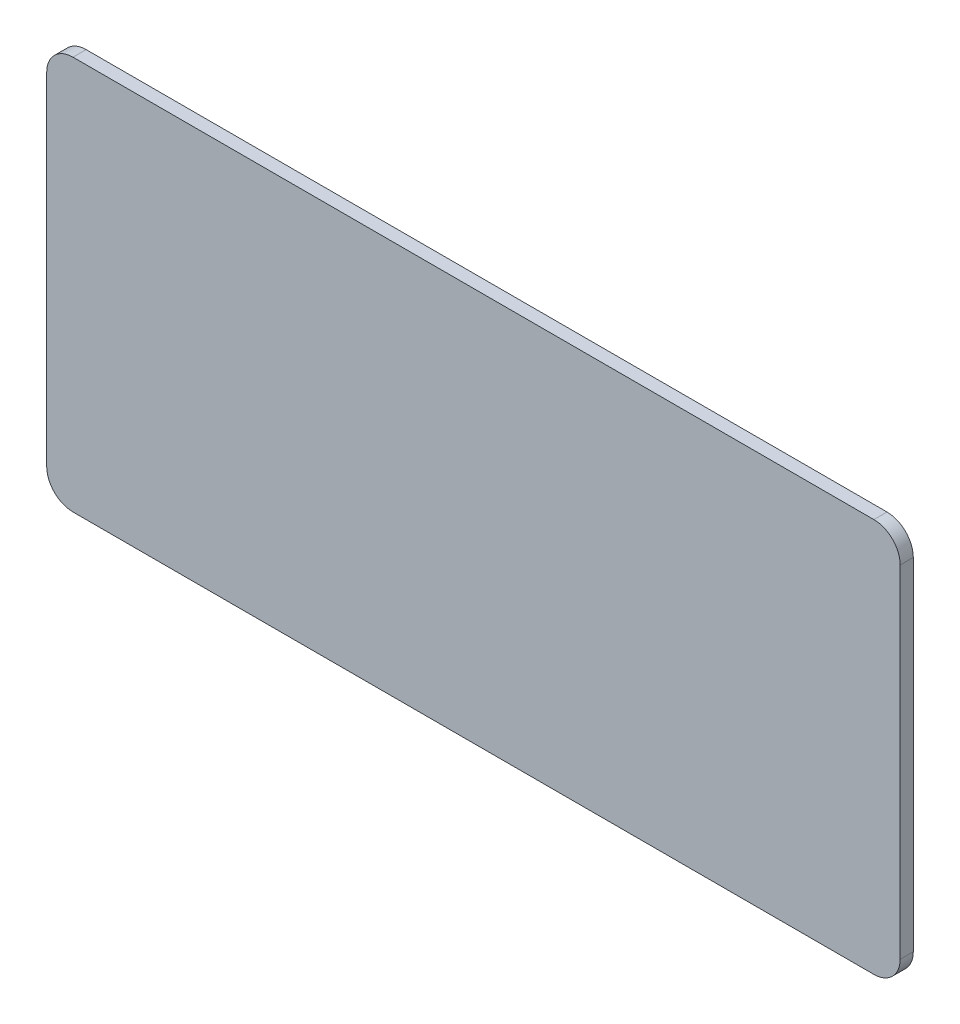
SolidWorks part; units mm, degrees
ref_plane "Front Plane" through (0, 0, 0) normal (0, 0, 1) x (1, 0, 0)
ref_plane "Top Plane" through (0, 0, 0) normal (0, 1, 0) x (1, 0, 0)
ref_plane "Right Plane" through (0, 0, 0) normal (1, 0, 0) x (0, 0, -1)
sketch "Sketch1" plane through (0, 0, 0) normal (0, 0, 1) x (1, 0, 0)
  line L0 (125.9407, 9.445) -> (125.9407, -9.555) construction
  line L1 (100.9407, 9.445) -> (150.9407, 9.445) construction
  line L2 (150.9407, -9.555) -> (100.9407, -9.555) construction
  line L3 (93.4407, 14.945) -> (93.4407, -15.055) construction
  line L4 (93.4407, -15.055) -> (158.4407, -15.055) construction
  line L5 (158.4407, -15.055) -> (158.4407, 14.945) construction
  line L6 (158.4407, 14.945) -> (93.4407, 14.945) construction
  line L7 (95.4407, 14.945) -> (95.4407, -15.055) construction
  line L8 (158.4407, -15.055) -> (93.4407, 14.945) construction
  line L9 (158.4407, 14.945) -> (93.4407, -15.055) construction
  line L10 (93.4407, -13.055) -> (158.4407, -13.055) construction
  line L11 (156.4407, -15.055) -> (156.4407, 14.945) construction
  line L12 (158.4407, 12.945) -> (93.4407, 12.945) construction
  line L13 (93.4407, -13.055) -> (93.4407, 12.945)
  line L14 (95.4407, 14.945) -> (156.4407, 14.945)
  line L15 (158.4407, 12.945) -> (158.4407, -13.055)
  line L16 (156.4407, -15.055) -> (95.4407, -15.055)
  arc A0 (93.4407, 12.945) -> (95.4407, 14.945) centre (95.4407, 12.945) cw
  arc A1 (156.4407, 14.945) -> (158.4407, 12.945) centre (156.4407, 12.945) cw
  arc A2 (158.4407, -13.055) -> (156.4407, -15.055) centre (156.4407, -13.055) cw
  arc A3 (95.4407, -15.055) -> (93.4407, -13.055) centre (95.4407, -13.055) cw
  point P6 (125.9407, -0.055)
  dimension "D1" = 65
  dimension "D2" = 30
  dimension "D3" = 2
extrude "Boss-Extrude1" add sketch "Sketch1" against normal blind 1
sketch "Sketch2" plane through (0, 0, -1) normal (0, 0, -1) x (-1, 0, 0)
  line L0 (-150.9407, 6.945) -> (-100.9407, 6.945) construction
  line L1 (-150.9407, -9.555) -> (-150.9407, 9.445) construction
  line L2 (-100.9407, -9.555) -> (-100.9407, 9.445) construction
  line L3 (-150.9407, -7.055) -> (-100.9407, -7.055) construction
  line L4 (-103.4407, 9.445) -> (-103.4407, -9.555) construction
  line L5 (-100.9407, 9.445) -> (-150.9407, 9.445) construction
  line L6 (-150.9407, -9.555) -> (-100.9407, -9.555) construction
  line L7 (-148.4407, 9.445) -> (-148.4407, -9.555) construction
  line L8 (-148.4407, 9.445) -> (-103.4407, 9.445)
  line L9 (-100.9407, 6.945) -> (-100.9407, -7.055)
  line L10 (-103.4407, -9.555) -> (-148.4407, -9.555)
  line L12 (-150.9407, -7.055) -> (-150.9407, 6.945)
  arc A0 (-150.9407, 6.945) -> (-148.4407, 9.445) centre (-148.4407, 6.945) cw
  arc A1 (-103.4407, 9.445) -> (-100.9407, 6.945) centre (-103.4407, 6.945) cw
  arc A2 (-103.4407, -9.555) -> (-100.9407, -7.055) centre (-103.4407, -7.055) ccw
  arc A3 (-148.4407, -9.555) -> (-150.9407, -7.055) centre (-148.4407, -7.055) cw
  dimension "D1" = 2.5
extrude "Boss-Extrude2" add sketch "Sketch2" along normal blind 1 separate body
